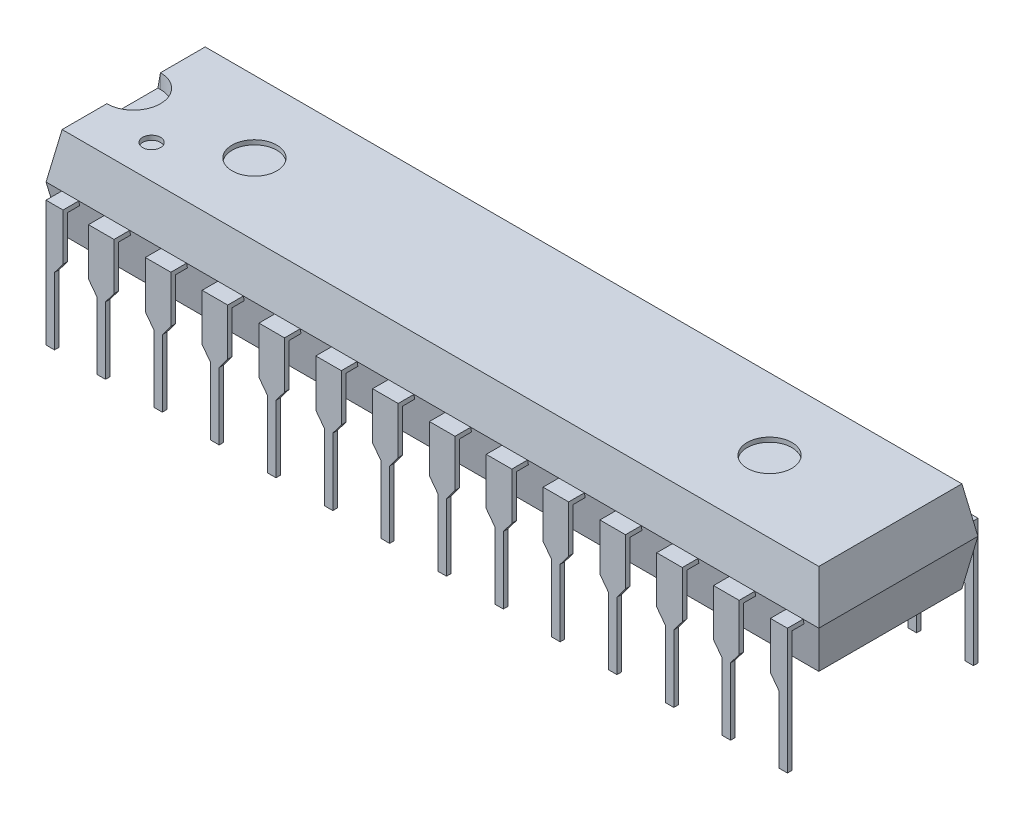
SolidWorks part; units mm, degrees
ref_plane "Front Plane" through (0, 0, 0) normal (0, 0, 1) x (1, 0, 0)
ref_plane "Top Plane" through (0, 0, 0) normal (0, 1, 0) x (1, 0, 0)
ref_plane "Right Plane" through (0, 0, 0) normal (1, 0, 0) x (0, 0, -1)
sketch "Sketch1" plane through (0, 0, 0) normal (0, 1, 0) x (1, 0, 0)
  line L1 (-17.27, -3.556) -> (17.27, -3.556)
  line L2 (-17.27, -3.556) -> (-17.27, 3.556)
  line L3 (-17.27, 3.556) -> (17.27, 3.556)
  line L4 (17.27, -3.556) -> (17.27, 3.556)
  line L5 (-17.27, -3.556) -> (17.27, 3.556) construction
  line L6 (-17.27, 3.556) -> (17.27, -3.556) construction
  point P0 (0, 0)
  dimension "D1" = 34.54
  dimension "D2" = 7.112
extrude "Boss-Extrude1" add sketch "Sketch1" along normal blind 2.0322 draft 10
mirror "Mirror1" about plane through (0, 0, 0) normal (0, 1, 0) of "Boss-Extrude1"
ref_plane "Plane1" through (0, 0, 4.056) normal (0, 0, 1) x (1, 0, 0)
sketch "Sketch2" plane through (0, 0, 4.056) normal (0, 0, 1) x (1, 0, 0)
  line L0 (16.57, 0) -> (15.808, 0)
  line L1 (-17.27, 0) -> (17.27, 0) construction
  line L2 (15.808, 0) -> (15.808, -2.1)
  line L3 (15.808, -2.1) -> (16.189, -2.608)
  line L4 (16.189, -2.608) -> (16.189, -5.608)
  line L5 (16.189, -5.608) -> (16.57, -5.608)
  line L6 (16.57, -5.608) -> (16.57, 0)
  point P4 (15.0518, -1.9019)
  point P9 (15.9041, -5.608)
  dimension "D1" = 0.762
  dimension "D2" = 0.381
  dimension "D3" = 3
  dimension "D4" = 0.508
  dimension "D5" = 2.1
  dimension "D6" = 0.7
extrude "Boss-Extrude2" add sketch "Sketch2" along normal blind 0.203 separate body
sketch "Sketch4" plane through (0, 0, 4.056) normal (0, 0, -1) x (-1, 0, 0)
  line L0 (-16.57, 0) -> (-15.808, 0) construction
  line L1 (-16.57, 0) -> (-15.808, 0)
  line L2 (-16.57, 0) -> (-16.57, -0.203)
  line L3 (-16.57, -0.203) -> (-15.808, -0.203)
  line L4 (-15.808, 0) -> (-15.808, -0.203)
  line L5 (-16.57, 0) -> (-15.808, -0.203) construction
  line L6 (-16.57, -0.203) -> (-15.808, 0) construction
  line L7 (-15.808, 0) -> (-15.808, -2.1) construction
  line L8 (-16.57, -5.608) -> (-16.57, 0) construction
  point P4 (-16.189, -0.1015)
  point P9 (-16.2641, 0)
  dimension "D1" = 0.203
extrude "Boss-Extrude3" add sketch "Sketch4" along normal up to next
mirror "Mirror5" about plane through (0, 0, 0) normal (1, 0, 0) of bodies 104
mirror "Mirror6" about plane through (0, 0, 0) normal (0, 0, 1) of bodies 105
sketch "Sketch5" plane through (0, 0, 4.056) normal (0, 0, 1) x (1, 0, 0)
  line L0 (13.268, 0) -> (14.411, 0)
  line L1 (-15.808, 0) -> (15.808, 0) construction
  line L2 (14.411, 0) -> (14.411, -2.1)
  line L3 (14.411, -2.1) -> (14.03, -2.608)
  line L4 (14.03, -2.608) -> (14.03, -5.608)
  line L5 (14.03, -5.608) -> (13.649, -5.608)
  line L6 (13.649, -5.608) -> (13.649, -2.608)
  line L7 (13.649, -2.608) -> (13.268, -2.1)
  line L8 (13.268, -2.1) -> (13.268, 0)
  line L10 (16.189, -5.608) -> (16.57, -5.608) construction
  line L11 (15.808, 0) -> (15.808, -2.1) construction
  line L13 (16.189, -2.608) -> (16.189, -5.608) construction
  point P8 (13.8395, -5.608)
  point P12 (13.8395, 0)
  point P16 (16.3795, -5.608)
  point P17 (13.4585, -2.354)
  dimension "D1" = 2.54
  dimension "D2" = 1.143
  dimension "D3" = 0.381
extrude "Boss-Extrude4" add sketch "Sketch5" along normal blind 0.203 separate body
sketch "Sketch6" plane through (0, 0, 4.056) normal (0, 0, -1) x (-1, 0, 0)
  line L0 (-14.411, -2.1) -> (-14.411, 0) construction
  line L1 (-13.268, 0) -> (-14.411, 0)
  line L2 (-13.268, 0) -> (-13.268, -0.203)
  line L3 (-13.268, -0.203) -> (-14.411, -0.203)
  line L4 (-14.411, 0) -> (-14.411, -0.203)
  line L5 (-13.268, 0) -> (-14.411, -0.203) construction
  line L6 (-13.268, -0.203) -> (-14.411, 0) construction
  point P4 (-13.8395, -0.1015)
  dimension "D1" = 0.203
extrude "Boss-Extrude5" add sketch "Sketch6" along normal up to next
pattern_linear "LPattern1" count 12 spacing 2.54 along (-1, 0, 0) of "Boss-Extrude4", "Boss-Extrude5"
mirror "Mirror7" about plane through (0, 0, 0) normal (0, 0, 1) of "LPattern1", "Boss-Extrude4", "Boss-Extrude5"
sketch "Sketch7" plane through (0, 2.0322, 0) normal (0, 1, 0) x (1, 0, 0)
  line L0 (-16.9117, 3.1977) -> (-16.9117, -3.1977) construction
  line L1 (-16.9117, 1.2) -> (-18.1826, 1.2)
  line L2 (-18.1826, 1.2) -> (-18.1826, -1.2)
  line L3 (-18.1826, -1.2) -> (-16.9117, -1.2)
  arc A0 (-16.9117, 1.2) -> (-16.9117, -1.2) centre (-16.9117, 0) cw
  dimension "D1" = 1.2
  dimension "D2" = 1.271
extrude "Cut-Extrude1" cut sketch "Sketch7" against normal blind 0.65
sketch "Sketch8" plane through (0, 2.0322, 0) normal (0, 1, 0) x (1, 0, 0)
  line L0 (-16.9117, 3.1977) -> (-16.9117, 1.2) construction
  circle A0 centre (-11.5117, 0) radius 1
  point P4 (0, 0)
  dimension "D1" = 2
  dimension "D2" = 5.4
extrude "Cut-Extrude2" cut sketch "Sketch8" against normal blind 0.2
mirror "Mirror8" about plane through (0, 0, 0) normal (1, 0, 0) of "Cut-Extrude2"
sketch "Sketch9" plane through (0, 2.0322, 0) normal (0, 1, 0) x (1, 0, 0)
  line L0 (-16.9117, -1.2) -> (-16.9117, -3.1977) construction
  line L1 (-16.9117, -3.1977) -> (16.9117, -3.1977) construction
  circle A0 centre (-14.4117, -1.6977) radius 0.4
  dimension "D1" = 0.8
  dimension "D2" = 2.5
  dimension "D3" = 1.5
extrude "Cut-Extrude3" cut sketch "Sketch9" against normal blind 0.2
